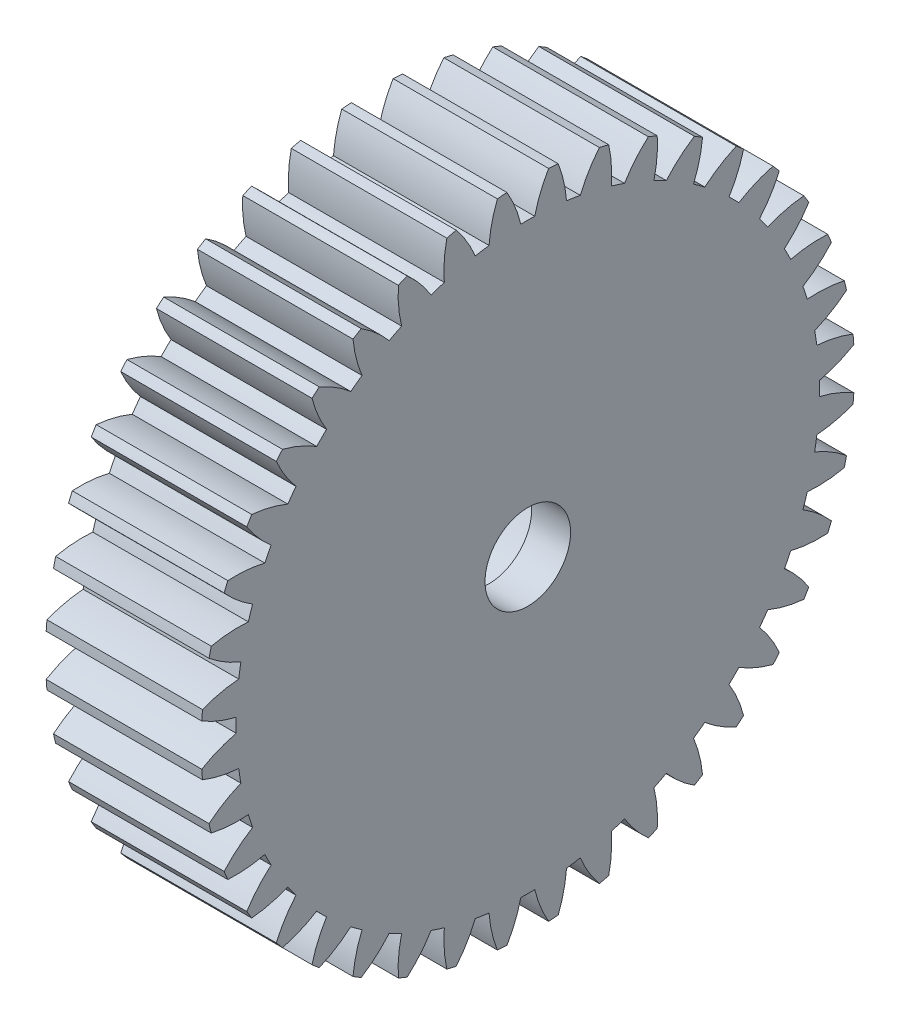
SolidWorks part; units mm, degrees
ref_plane "Front Plane" through (0, 0, 0) normal (0, 0, 1) x (1, 0, 0)
ref_plane "Top Plane" through (0, 0, 0) normal (0, 1, 0) x (1, 0, 0)
ref_plane "Right Plane" through (0, 0, 0) normal (1, 0, 0) x (0, 0, -1)
ref_plane "Plane1" through (-1.595, 0, 0) normal (1, 0, 0) x (0, 0, -1)
sketch "Sketch1" plane through (-1.595, 0, 0) normal (1, 0, 0) x (0, 0, -1)
  circle B0 centre (0, 0) radius 0.4
  arc B1 (-8.3829, 0.5357) -> (-7.4969, 0.179) centre (-6.7581, 3.2926) ccw
  arc B2 (-7.4969, 0.179) -> (-7.4969, -0.179) centre (0, 0) ccw
  arc B3 (-7.4969, -0.179) -> (-8.3829, -0.5357) centre (-6.7581, -3.2926) ccw
  arc B4 (-8.3829, -0.5357) -> (-8.3635, -0.7822) centre (0, 0) ccw
  arc B5 (-8.3635, -0.7822) -> (-7.4326, -0.996) centre (-7.19, 2.1948) ccw
  arc B6 (-7.4326, -0.996) -> (-7.3766, -1.3496) centre (0, 0) ccw
  arc B7 (-7.3766, -1.3496) -> (-8.1959, -1.8405) centre (-6.1599, -4.3092) ccw
  arc B8 (-8.1959, -1.8405) -> (-8.1382, -2.081) centre (0, 0) ccw
  arc B9 (-8.1382, -2.081) -> (-7.1853, -2.1464) centre (-7.4448, 1.043) ccw
  arc B10 (-7.1853, -2.1464) -> (-7.0746, -2.4869) centre (0, 0) ccw
  arc B11 (-7.0746, -2.4869) -> (-7.8071, -3.1) centre (-5.4099, -5.2198) ccw
  arc B12 (-7.8071, -3.1) -> (-7.7124, -3.3284) centre (0, 0) ccw
  arc B13 (-7.7124, -3.3284) -> (-6.761, -3.244) centre (-7.5163, -0.1344) ccw
  arc B14 (-6.761, -3.244) -> (-6.5985, -3.563) centre (0, 0) ccw
  arc B15 (-6.5985, -3.563) -> (-7.226, -4.2831) centre (-4.5268, -6.0018) ccw
  arc B16 (-7.226, -4.2831) -> (-7.0968, -4.4939) centre (0, 0) ccw
  arc B17 (-7.0968, -4.4939) -> (-6.1703, -4.2617) centre (-7.4028, -1.3086) ccw
  arc B18 (-6.1703, -4.2617) -> (-5.9599, -4.5514) centre (0, 0) ccw
  arc B19 (-5.9599, -4.5514) -> (-6.467, -5.3608) centre (-3.5321, -6.6361) ccw
  arc B20 (-6.467, -5.3608) -> (-6.3064, -5.5488) centre (0, 0) ccw
  arc B21 (-6.3064, -5.5488) -> (-5.4277, -5.1745) centre (-7.1069, -2.4505) ccw
  arc B22 (-5.4277, -5.1745) -> (-5.1745, -5.4277) centre (0, 0) ccw
  arc B23 (-5.1745, -5.4277) -> (-5.5488, -6.3064) centre (-2.4505, -7.1069) ccw
  arc B24 (-5.5488, -6.3064) -> (-5.3608, -6.467) centre (0, 0) ccw
  arc B25 (-5.3608, -6.467) -> (-4.5514, -5.9599) centre (-6.6361, -3.5321) ccw
  arc B26 (-4.5514, -5.9599) -> (-4.2617, -6.1703) centre (0, 0) ccw
  arc B27 (-4.2617, -6.1703) -> (-4.4939, -7.0968) centre (-1.3086, -7.4028) ccw
  arc B28 (-4.4939, -7.0968) -> (-4.2831, -7.226) centre (0, 0) ccw
  arc B29 (-4.2831, -7.226) -> (-3.563, -6.5985) centre (-6.0018, -4.5268) ccw
  arc B30 (-3.563, -6.5985) -> (-3.244, -6.761) centre (0, 0) ccw
  arc B31 (-3.244, -6.761) -> (-3.3284, -7.7124) centre (-0.1344, -7.5163) ccw
  arc B32 (-3.3284, -7.7124) -> (-3.1, -7.8071) centre (0, 0) ccw
  arc B33 (-3.1, -7.8071) -> (-2.4869, -7.0746) centre (-5.2198, -5.4099) ccw
  arc B34 (-2.4869, -7.0746) -> (-2.1464, -7.1853) centre (0, 0) ccw
  arc B35 (-2.1464, -7.1853) -> (-2.081, -8.1382) centre (1.043, -7.4448) ccw
  arc B36 (-2.081, -8.1382) -> (-1.8405, -8.1959) centre (0, 0) ccw
  arc B37 (-1.8405, -8.1959) -> (-1.3496, -7.3766) centre (-4.3092, -6.1599) ccw
  arc B38 (-1.3496, -7.3766) -> (-0.996, -7.4326) centre (0, 0) ccw
  arc B39 (-0.996, -7.4326) -> (-0.7822, -8.3635) centre (2.1948, -7.19) ccw
  arc B40 (-0.7822, -8.3635) -> (-0.5357, -8.3829) centre (0, 0) ccw
  arc B41 (-0.5357, -8.3829) -> (-0.179, -7.4969) centre (-3.2926, -6.7581) ccw
  arc B42 (-0.179, -7.4969) -> (0.179, -7.4969) centre (0, 0) ccw
  arc B43 (0.179, -7.4969) -> (0.5357, -8.3829) centre (3.2926, -6.7581) ccw
  arc B44 (0.5357, -8.3829) -> (0.7822, -8.3635) centre (0, 0) ccw
  arc B45 (0.7822, -8.3635) -> (0.996, -7.4326) centre (-2.1948, -7.19) ccw
  arc B46 (0.996, -7.4326) -> (1.3496, -7.3766) centre (0, 0) ccw
  arc B47 (1.3496, -7.3766) -> (1.8405, -8.1959) centre (4.3092, -6.1599) ccw
  arc B48 (1.8405, -8.1959) -> (2.081, -8.1382) centre (0, 0) ccw
  arc B49 (2.081, -8.1382) -> (2.1464, -7.1853) centre (-1.043, -7.4448) ccw
  arc B50 (2.1464, -7.1853) -> (2.4869, -7.0746) centre (0, 0) ccw
  arc B51 (2.4869, -7.0746) -> (3.1, -7.8071) centre (5.2198, -5.4099) ccw
  arc B52 (3.1, -7.8071) -> (3.3284, -7.7124) centre (0, 0) ccw
  arc B53 (3.3284, -7.7124) -> (3.244, -6.761) centre (0.1344, -7.5163) ccw
  arc B54 (3.244, -6.761) -> (3.563, -6.5985) centre (0, 0) ccw
  arc B55 (3.563, -6.5985) -> (4.2831, -7.226) centre (6.0018, -4.5268) ccw
  arc B56 (4.2831, -7.226) -> (4.4939, -7.0968) centre (0, 0) ccw
  arc B57 (4.4939, -7.0968) -> (4.2617, -6.1703) centre (1.3086, -7.4028) ccw
  arc B58 (4.2617, -6.1703) -> (4.5514, -5.9599) centre (0, 0) ccw
  arc B59 (4.5514, -5.9599) -> (5.3608, -6.467) centre (6.6361, -3.5321) ccw
  arc B60 (5.3608, -6.467) -> (5.5488, -6.3064) centre (0, 0) ccw
  arc B61 (5.5488, -6.3064) -> (5.1745, -5.4277) centre (2.4505, -7.1069) ccw
  arc B62 (5.1745, -5.4277) -> (5.4277, -5.1745) centre (0, 0) ccw
  arc B63 (5.4277, -5.1745) -> (6.3064, -5.5488) centre (7.1069, -2.4505) ccw
  arc B64 (6.3064, -5.5488) -> (6.467, -5.3608) centre (0, 0) ccw
  arc B65 (6.467, -5.3608) -> (5.9599, -4.5514) centre (3.5321, -6.6361) ccw
  arc B66 (5.9599, -4.5514) -> (6.1703, -4.2617) centre (0, 0) ccw
  arc B67 (6.1703, -4.2617) -> (7.0968, -4.4939) centre (7.4028, -1.3086) ccw
  arc B68 (7.0968, -4.4939) -> (7.226, -4.2831) centre (0, 0) ccw
  arc B69 (7.226, -4.2831) -> (6.5985, -3.563) centre (4.5268, -6.0018) ccw
  arc B70 (6.5985, -3.563) -> (6.761, -3.244) centre (0, 0) ccw
  arc B71 (6.761, -3.244) -> (7.7124, -3.3284) centre (7.5163, -0.1344) ccw
  arc B72 (7.7124, -3.3284) -> (7.8071, -3.1) centre (0, 0) ccw
  arc B73 (7.8071, -3.1) -> (7.0746, -2.4869) centre (5.4099, -5.2198) ccw
  arc B74 (7.0746, -2.4869) -> (7.1853, -2.1464) centre (0, 0) ccw
  arc B75 (7.1853, -2.1464) -> (8.1382, -2.081) centre (7.4448, 1.043) ccw
  arc B76 (8.1382, -2.081) -> (8.1959, -1.8405) centre (0, 0) ccw
  arc B77 (8.1959, -1.8405) -> (7.3766, -1.3496) centre (6.1599, -4.3092) ccw
  arc B78 (7.3766, -1.3496) -> (7.4326, -0.996) centre (0, 0) ccw
  arc B79 (7.4326, -0.996) -> (8.3635, -0.7822) centre (7.19, 2.1948) ccw
  arc B80 (8.3635, -0.7822) -> (8.3829, -0.5357) centre (0, 0) ccw
  arc B81 (8.3829, -0.5357) -> (7.4969, -0.179) centre (6.7581, -3.2926) ccw
  arc B82 (7.4969, -0.179) -> (7.4969, 0.179) centre (0, 0) ccw
  arc B83 (7.4969, 0.179) -> (8.3829, 0.5357) centre (6.7581, 3.2926) ccw
  arc B84 (8.3829, 0.5357) -> (8.3635, 0.7822) centre (0, 0) ccw
  arc B85 (8.3635, 0.7822) -> (7.4326, 0.996) centre (7.19, -2.1948) ccw
  arc B86 (7.4326, 0.996) -> (7.3766, 1.3496) centre (0, 0) ccw
  arc B87 (7.3766, 1.3496) -> (8.1959, 1.8405) centre (6.1599, 4.3092) ccw
  arc B88 (8.1959, 1.8405) -> (8.1382, 2.081) centre (0, 0) ccw
  arc B89 (8.1382, 2.081) -> (7.1853, 2.1464) centre (7.4448, -1.043) ccw
  arc B90 (7.1853, 2.1464) -> (7.0746, 2.4869) centre (0, 0) ccw
  arc B91 (7.0746, 2.4869) -> (7.8071, 3.1) centre (5.4099, 5.2198) ccw
  arc B92 (7.8071, 3.1) -> (7.7124, 3.3284) centre (0, 0) ccw
  arc B93 (7.7124, 3.3284) -> (6.761, 3.244) centre (7.5163, 0.1344) ccw
  arc B94 (6.761, 3.244) -> (6.5985, 3.563) centre (0, 0) ccw
  arc B95 (6.5985, 3.563) -> (7.226, 4.2831) centre (4.5268, 6.0018) ccw
  arc B96 (7.226, 4.2831) -> (7.0968, 4.4939) centre (0, 0) ccw
  arc B97 (7.0968, 4.4939) -> (6.1703, 4.2617) centre (7.4028, 1.3086) ccw
  arc B98 (6.1703, 4.2617) -> (5.9599, 4.5514) centre (0, 0) ccw
  arc B99 (5.9599, 4.5514) -> (6.467, 5.3608) centre (3.5321, 6.6361) ccw
  arc B100 (6.467, 5.3608) -> (6.3064, 5.5488) centre (0, 0) ccw
  arc B101 (6.3064, 5.5488) -> (5.4277, 5.1745) centre (7.1069, 2.4505) ccw
  arc B102 (5.4277, 5.1745) -> (5.1745, 5.4277) centre (0, 0) ccw
  arc B103 (5.1745, 5.4277) -> (5.5488, 6.3064) centre (2.4505, 7.1069) ccw
  arc B104 (5.5488, 6.3064) -> (5.3608, 6.467) centre (0, 0) ccw
  arc B105 (5.3608, 6.467) -> (4.5514, 5.9599) centre (6.6361, 3.5321) ccw
  arc B106 (4.5514, 5.9599) -> (4.2617, 6.1703) centre (0, 0) ccw
  arc B107 (4.2617, 6.1703) -> (4.4939, 7.0968) centre (1.3086, 7.4028) ccw
  arc B108 (4.4939, 7.0968) -> (4.2831, 7.226) centre (0, 0) ccw
  arc B109 (4.2831, 7.226) -> (3.563, 6.5985) centre (6.0018, 4.5268) ccw
  arc B110 (3.563, 6.5985) -> (3.244, 6.761) centre (0, 0) ccw
  arc B111 (3.244, 6.761) -> (3.3284, 7.7124) centre (0.1344, 7.5163) ccw
  arc B112 (3.3284, 7.7124) -> (3.1, 7.8071) centre (0, 0) ccw
  arc B113 (3.1, 7.8071) -> (2.4869, 7.0746) centre (5.2198, 5.4099) ccw
  arc B114 (2.4869, 7.0746) -> (2.1464, 7.1853) centre (0, 0) ccw
  arc B115 (2.1464, 7.1853) -> (2.081, 8.1382) centre (-1.043, 7.4448) ccw
  arc B116 (2.081, 8.1382) -> (1.8405, 8.1959) centre (0, 0) ccw
  arc B117 (1.8405, 8.1959) -> (1.3496, 7.3766) centre (4.3092, 6.1599) ccw
  arc B118 (1.3496, 7.3766) -> (0.996, 7.4326) centre (0, 0) ccw
  arc B119 (0.996, 7.4326) -> (0.7822, 8.3635) centre (-2.1948, 7.19) ccw
  arc B120 (0.7822, 8.3635) -> (0.5357, 8.3829) centre (0, 0) ccw
  arc B121 (0.5357, 8.3829) -> (0.179, 7.4969) centre (3.2926, 6.7581) ccw
  arc B122 (0.179, 7.4969) -> (-0.179, 7.4969) centre (0, 0) ccw
  arc B123 (-0.179, 7.4969) -> (-0.5357, 8.3829) centre (-3.2926, 6.7581) ccw
  arc B124 (-0.5357, 8.3829) -> (-0.7822, 8.3635) centre (0, 0) ccw
  arc B125 (-0.7822, 8.3635) -> (-0.996, 7.4326) centre (2.1948, 7.19) ccw
  arc B126 (-0.996, 7.4326) -> (-1.3496, 7.3766) centre (0, 0) ccw
  arc B127 (-1.3496, 7.3766) -> (-1.8405, 8.1959) centre (-4.3092, 6.1599) ccw
  arc B128 (-1.8405, 8.1959) -> (-2.081, 8.1382) centre (0, 0) ccw
  arc B129 (-2.081, 8.1382) -> (-2.1464, 7.1853) centre (1.043, 7.4448) ccw
  arc B130 (-2.1464, 7.1853) -> (-2.4869, 7.0746) centre (0, 0) ccw
  arc B131 (-2.4869, 7.0746) -> (-3.1, 7.8071) centre (-5.2198, 5.4099) ccw
  arc B132 (-3.1, 7.8071) -> (-3.3284, 7.7124) centre (0, 0) ccw
  arc B133 (-3.3284, 7.7124) -> (-3.244, 6.761) centre (-0.1344, 7.5163) ccw
  arc B134 (-3.244, 6.761) -> (-3.563, 6.5985) centre (0, 0) ccw
  arc B135 (-3.563, 6.5985) -> (-4.2831, 7.226) centre (-6.0018, 4.5268) ccw
  arc B136 (-4.2831, 7.226) -> (-4.4939, 7.0968) centre (0, 0) ccw
  arc B137 (-4.4939, 7.0968) -> (-4.2617, 6.1703) centre (-1.3086, 7.4028) ccw
  arc B138 (-4.2617, 6.1703) -> (-4.5514, 5.9599) centre (0, 0) ccw
  arc B139 (-4.5514, 5.9599) -> (-5.3608, 6.467) centre (-6.6361, 3.5321) ccw
  arc B140 (-5.3608, 6.467) -> (-5.5488, 6.3064) centre (0, 0) ccw
  arc B141 (-5.5488, 6.3064) -> (-5.1745, 5.4277) centre (-2.4505, 7.1069) ccw
  arc B142 (-5.1745, 5.4277) -> (-5.4277, 5.1745) centre (0, 0) ccw
  arc B143 (-5.4277, 5.1745) -> (-6.3064, 5.5488) centre (-7.1069, 2.4505) ccw
  arc B144 (-6.3064, 5.5488) -> (-6.467, 5.3608) centre (0, 0) ccw
  arc B145 (-6.467, 5.3608) -> (-5.9599, 4.5514) centre (-3.5321, 6.6361) ccw
  arc B146 (-5.9599, 4.5514) -> (-6.1703, 4.2617) centre (0, 0) ccw
  arc B147 (-6.1703, 4.2617) -> (-7.0968, 4.4939) centre (-7.4028, 1.3086) ccw
  arc B148 (-7.0968, 4.4939) -> (-7.226, 4.2831) centre (0, 0) ccw
  arc B149 (-7.226, 4.2831) -> (-6.5985, 3.563) centre (-4.5268, 6.0018) ccw
  arc B150 (-6.5985, 3.563) -> (-6.761, 3.244) centre (0, 0) ccw
  arc B151 (-6.761, 3.244) -> (-7.7124, 3.3284) centre (-7.5163, 0.1344) ccw
  arc B152 (-7.7124, 3.3284) -> (-7.8071, 3.1) centre (0, 0) ccw
  arc B153 (-7.8071, 3.1) -> (-7.0746, 2.4869) centre (-5.4099, 5.2198) ccw
  arc B154 (-7.0746, 2.4869) -> (-7.1853, 2.1464) centre (0, 0) ccw
  arc B155 (-7.1853, 2.1464) -> (-8.1382, 2.081) centre (-7.4448, -1.043) ccw
  arc B156 (-8.1382, 2.081) -> (-8.1959, 1.8405) centre (0, 0) ccw
  arc B157 (-8.1959, 1.8405) -> (-7.3766, 1.3496) centre (-6.1599, 4.3092) ccw
  arc B158 (-7.3766, 1.3496) -> (-7.4326, 0.996) centre (0, 0) ccw
  arc B159 (-7.4326, 0.996) -> (-8.3635, 0.7822) centre (-7.19, -2.1948) ccw
  arc B160 (-8.3635, 0.7822) -> (-8.3829, 0.5357) centre (0, 0) ccw
sketch_block_instance "Block2-1"
sketch_block "Block2"
extrude "Boss-Extrude1" add sketch "Sketch1" against normal blind 3
sketch "Sketch4" plane through (-1.595, 0, 0) normal (1, 0, 0) x (0, 0, -1)
  circle A0 centre (0, 0) radius 2.4375
  dimension "D1" = 4.875
extrude "Cut-Extrude2" cut sketch "Sketch4" against normal through all
sketch "Sketch5" plane through (-1.595, 0, 0) normal (1, 0, 0) x (0, 0, -1)
  arc A160 (-8.3635, 0.7822) -> (-8.3829, 0.5357) centre (0, 0) ccw
  arc A161 (-8.3829, 0.5357) -> (-7.4969, 0.179) centre (-6.7581, 3.2926) ccw
  arc A162 (-7.4969, 0.179) -> (-7.4969, -0.179) centre (0, 0) ccw
  arc A163 (-7.4969, -0.179) -> (-8.3829, -0.5357) centre (-6.7581, -3.2926) ccw
  arc A164 (-8.3829, -0.5357) -> (-8.3635, -0.7822) centre (0, 0) ccw
  arc A165 (-8.3635, -0.7822) -> (-7.4326, -0.996) centre (-7.19, 2.1948) ccw
  arc A166 (-7.4326, -0.996) -> (-7.3766, -1.3496) centre (0, 0) ccw
  arc A167 (-7.3766, -1.3496) -> (-8.1959, -1.8405) centre (-6.1599, -4.3092) ccw
  arc A168 (-8.1959, -1.8405) -> (-8.1382, -2.081) centre (0, 0) ccw
  arc A169 (-8.1382, -2.081) -> (-7.1853, -2.1464) centre (-7.4448, 1.043) ccw
  arc A170 (-7.1853, -2.1464) -> (-7.0746, -2.4869) centre (0, 0) ccw
  arc A171 (-7.0746, -2.4869) -> (-7.8071, -3.1) centre (-5.4099, -5.2198) ccw
  arc A172 (-7.8071, -3.1) -> (-7.7124, -3.3284) centre (0, 0) ccw
  arc A173 (-7.7124, -3.3284) -> (-6.761, -3.244) centre (-7.5163, -0.1344) ccw
  arc A174 (-6.761, -3.244) -> (-6.5985, -3.563) centre (0, 0) ccw
  arc A175 (-6.5985, -3.563) -> (-7.226, -4.2831) centre (-4.5268, -6.0018) ccw
  arc A176 (-7.226, -4.2831) -> (-7.0968, -4.4939) centre (0, 0) ccw
  arc A177 (-7.0968, -4.4939) -> (-6.1703, -4.2617) centre (-7.4028, -1.3086) ccw
  arc A178 (-6.1703, -4.2617) -> (-5.9599, -4.5514) centre (0, 0) ccw
  arc A179 (-5.9599, -4.5514) -> (-6.467, -5.3608) centre (-3.5321, -6.6361) ccw
  arc A180 (-6.467, -5.3608) -> (-6.3064, -5.5488) centre (0, 0) ccw
  arc A181 (-6.3064, -5.5488) -> (-5.4277, -5.1745) centre (-7.1069, -2.4505) ccw
  arc A182 (-5.4277, -5.1745) -> (-5.1745, -5.4277) centre (0, 0) ccw
  arc A183 (-5.1745, -5.4277) -> (-5.5488, -6.3064) centre (-2.4505, -7.1069) ccw
  arc A184 (-5.5488, -6.3064) -> (-5.3608, -6.467) centre (0, 0) ccw
  arc A185 (-5.3608, -6.467) -> (-4.5514, -5.9599) centre (-6.6361, -3.5321) ccw
  arc A186 (-4.5514, -5.9599) -> (-4.2617, -6.1703) centre (0, 0) ccw
  arc A187 (-4.2617, -6.1703) -> (-4.4939, -7.0968) centre (-1.3086, -7.4028) ccw
  arc A188 (-4.4939, -7.0968) -> (-4.2831, -7.226) centre (0, 0) ccw
  arc A189 (-4.2831, -7.226) -> (-3.563, -6.5985) centre (-6.0018, -4.5268) ccw
  arc A190 (-3.563, -6.5985) -> (-3.244, -6.761) centre (0, 0) ccw
  arc A191 (-3.244, -6.761) -> (-3.3284, -7.7124) centre (-0.1344, -7.5163) ccw
  arc A192 (-3.3284, -7.7124) -> (-3.1, -7.8071) centre (0, 0) ccw
  arc A193 (-3.1, -7.8071) -> (-2.4869, -7.0746) centre (-5.2198, -5.4099) ccw
  arc A194 (-2.4869, -7.0746) -> (-2.1464, -7.1853) centre (0, 0) ccw
  arc A195 (-2.1464, -7.1853) -> (-2.081, -8.1382) centre (1.043, -7.4448) ccw
  arc A196 (-2.081, -8.1382) -> (-1.8405, -8.1959) centre (0, 0) ccw
  arc A197 (-1.8405, -8.1959) -> (-1.3496, -7.3766) centre (-4.3092, -6.1599) ccw
  arc A198 (-1.3496, -7.3766) -> (-0.996, -7.4326) centre (0, 0) ccw
  arc A199 (-0.996, -7.4326) -> (-0.7822, -8.3635) centre (2.1948, -7.19) ccw
  arc A200 (-0.7822, -8.3635) -> (-0.5357, -8.3829) centre (0, 0) ccw
  arc A201 (-0.5357, -8.3829) -> (-0.179, -7.4969) centre (-3.2926, -6.7581) ccw
  arc A202 (-0.179, -7.4969) -> (0.179, -7.4969) centre (0, 0) ccw
  arc A203 (0.179, -7.4969) -> (0.5357, -8.3829) centre (3.2926, -6.7581) ccw
  arc A204 (0.5357, -8.3829) -> (0.7822, -8.3635) centre (0, 0) ccw
  arc A205 (0.7822, -8.3635) -> (0.996, -7.4326) centre (-2.1948, -7.19) ccw
  arc A206 (0.996, -7.4326) -> (1.3496, -7.3766) centre (0, 0) ccw
  arc A207 (1.3496, -7.3766) -> (1.8405, -8.1959) centre (4.3092, -6.1599) ccw
  arc A208 (1.8405, -8.1959) -> (2.081, -8.1382) centre (0, 0) ccw
  arc A209 (2.081, -8.1382) -> (2.1464, -7.1853) centre (-1.043, -7.4448) ccw
  arc A210 (2.1464, -7.1853) -> (2.4869, -7.0746) centre (0, 0) ccw
  arc A211 (2.4869, -7.0746) -> (3.1, -7.8071) centre (5.2198, -5.4099) ccw
  arc A212 (3.1, -7.8071) -> (3.3284, -7.7124) centre (0, 0) ccw
  arc A213 (3.3284, -7.7124) -> (3.244, -6.761) centre (0.1344, -7.5163) ccw
  arc A214 (3.244, -6.761) -> (3.563, -6.5985) centre (0, 0) ccw
  arc A215 (3.563, -6.5985) -> (4.2831, -7.226) centre (6.0018, -4.5268) ccw
  arc A216 (4.2831, -7.226) -> (4.4939, -7.0968) centre (0, 0) ccw
  arc A217 (4.4939, -7.0968) -> (4.2617, -6.1703) centre (1.3086, -7.4028) ccw
  arc A218 (4.2617, -6.1703) -> (4.5514, -5.9599) centre (0, 0) ccw
  arc A219 (4.5514, -5.9599) -> (5.3608, -6.467) centre (6.6361, -3.5321) ccw
  arc A220 (5.3608, -6.467) -> (5.5488, -6.3064) centre (0, 0) ccw
  arc A221 (5.5488, -6.3064) -> (5.1745, -5.4277) centre (2.4505, -7.1069) ccw
  arc A222 (5.1745, -5.4277) -> (5.4277, -5.1745) centre (0, 0) ccw
  arc A223 (5.4277, -5.1745) -> (6.3064, -5.5488) centre (7.1069, -2.4505) ccw
  arc A224 (6.3064, -5.5488) -> (6.467, -5.3608) centre (0, 0) ccw
  arc A225 (6.467, -5.3608) -> (5.9599, -4.5514) centre (3.5321, -6.6361) ccw
  arc A226 (5.9599, -4.5514) -> (6.1703, -4.2617) centre (0, 0) ccw
  arc A227 (6.1703, -4.2617) -> (7.0968, -4.4939) centre (7.4028, -1.3086) ccw
  arc A228 (7.0968, -4.4939) -> (7.226, -4.2831) centre (0, 0) ccw
  arc A229 (7.226, -4.2831) -> (6.5985, -3.563) centre (4.5268, -6.0018) ccw
  arc A230 (6.5985, -3.563) -> (6.761, -3.244) centre (0, 0) ccw
  arc A231 (6.761, -3.244) -> (7.7124, -3.3284) centre (7.5163, -0.1344) ccw
  arc A232 (7.7124, -3.3284) -> (7.8071, -3.1) centre (0, 0) ccw
  arc A233 (7.8071, -3.1) -> (7.0746, -2.4869) centre (5.4099, -5.2198) ccw
  arc A234 (7.0746, -2.4869) -> (7.1853, -2.1464) centre (0, 0) ccw
  arc A235 (7.1853, -2.1464) -> (8.1382, -2.081) centre (7.4448, 1.043) ccw
  arc A236 (8.1382, -2.081) -> (8.1959, -1.8405) centre (0, 0) ccw
  arc A237 (8.1959, -1.8405) -> (7.3766, -1.3496) centre (6.1599, -4.3092) ccw
  arc A238 (7.3766, -1.3496) -> (7.4326, -0.996) centre (0, 0) ccw
  arc A239 (7.4326, -0.996) -> (8.3635, -0.7822) centre (7.19, 2.1948) ccw
  arc A240 (8.3635, -0.7822) -> (8.3829, -0.5357) centre (0, 0) ccw
  arc A241 (8.3829, -0.5357) -> (7.4969, -0.179) centre (6.7581, -3.2926) ccw
  arc A242 (7.4969, -0.179) -> (7.4969, 0.179) centre (0, 0) ccw
  arc A243 (7.4969, 0.179) -> (8.3829, 0.5357) centre (6.7581, 3.2926) ccw
  arc A244 (8.3829, 0.5357) -> (8.3635, 0.7822) centre (0, 0) ccw
  arc A245 (8.3635, 0.7822) -> (7.4326, 0.996) centre (7.19, -2.1948) ccw
  arc A246 (7.4326, 0.996) -> (7.3766, 1.3496) centre (0, 0) ccw
  arc A247 (7.3766, 1.3496) -> (8.1959, 1.8405) centre (6.1599, 4.3092) ccw
  arc A248 (8.1959, 1.8405) -> (8.1382, 2.081) centre (0, 0) ccw
  arc A249 (8.1382, 2.081) -> (7.1853, 2.1464) centre (7.4448, -1.043) ccw
  arc A250 (7.1853, 2.1464) -> (7.0746, 2.4869) centre (0, 0) ccw
  arc A251 (7.0746, 2.4869) -> (7.8071, 3.1) centre (5.4099, 5.2198) ccw
  arc A252 (7.8071, 3.1) -> (7.7124, 3.3284) centre (0, 0) ccw
  arc A253 (7.7124, 3.3284) -> (6.761, 3.244) centre (7.5163, 0.1344) ccw
  arc A254 (6.761, 3.244) -> (6.5985, 3.563) centre (0, 0) ccw
  arc A255 (6.5985, 3.563) -> (7.226, 4.2831) centre (4.5268, 6.0018) ccw
  arc A256 (7.226, 4.2831) -> (7.0968, 4.4939) centre (0, 0) ccw
  arc A257 (7.0968, 4.4939) -> (6.1703, 4.2617) centre (7.4028, 1.3086) ccw
  arc A258 (6.1703, 4.2617) -> (5.9599, 4.5514) centre (0, 0) ccw
  arc A259 (5.9599, 4.5514) -> (6.467, 5.3608) centre (3.5321, 6.6361) ccw
  arc A260 (6.467, 5.3608) -> (6.3064, 5.5488) centre (0, 0) ccw
  arc A261 (6.3064, 5.5488) -> (5.4277, 5.1745) centre (7.1069, 2.4505) ccw
  arc A262 (5.4277, 5.1745) -> (5.1745, 5.4277) centre (0, 0) ccw
  arc A263 (5.1745, 5.4277) -> (5.5488, 6.3064) centre (2.4505, 7.1069) ccw
  arc A264 (5.5488, 6.3064) -> (5.3608, 6.467) centre (0, 0) ccw
  arc A265 (5.3608, 6.467) -> (4.5514, 5.9599) centre (6.6361, 3.5321) ccw
  arc A266 (4.5514, 5.9599) -> (4.2617, 6.1703) centre (0, 0) ccw
  arc A267 (4.2617, 6.1703) -> (4.4939, 7.0968) centre (1.3086, 7.4028) ccw
  arc A268 (4.4939, 7.0968) -> (4.2831, 7.226) centre (0, 0) ccw
  arc A269 (4.2831, 7.226) -> (3.563, 6.5985) centre (6.0018, 4.5268) ccw
  arc A270 (3.563, 6.5985) -> (3.244, 6.761) centre (0, 0) ccw
  arc A271 (3.244, 6.761) -> (3.3284, 7.7124) centre (0.1344, 7.5163) ccw
  arc A272 (3.3284, 7.7124) -> (3.1, 7.8071) centre (0, 0) ccw
  arc A273 (3.1, 7.8071) -> (2.4869, 7.0746) centre (5.2198, 5.4099) ccw
  arc A274 (2.4869, 7.0746) -> (2.1464, 7.1853) centre (0, 0) ccw
  arc A275 (2.1464, 7.1853) -> (2.081, 8.1382) centre (-1.043, 7.4448) ccw
  arc A276 (2.081, 8.1382) -> (1.8405, 8.1959) centre (0, 0) ccw
  arc A277 (1.8405, 8.1959) -> (1.3496, 7.3766) centre (4.3092, 6.1599) ccw
  arc A278 (1.3496, 7.3766) -> (0.996, 7.4326) centre (0, 0) ccw
  arc A279 (0.996, 7.4326) -> (0.7822, 8.3635) centre (-2.1948, 7.19) ccw
  arc A280 (0.7822, 8.3635) -> (0.5357, 8.3829) centre (0, 0) ccw
  arc A281 (0.5357, 8.3829) -> (0.179, 7.4969) centre (3.2926, 6.7581) ccw
  arc A282 (0.179, 7.4969) -> (-0.179, 7.4969) centre (0, 0) ccw
  arc A283 (-0.179, 7.4969) -> (-0.5357, 8.3829) centre (-3.2926, 6.7581) ccw
  arc A284 (-0.5357, 8.3829) -> (-0.7822, 8.3635) centre (0, 0) ccw
  arc A285 (-0.7822, 8.3635) -> (-0.996, 7.4326) centre (2.1948, 7.19) ccw
  arc A286 (-0.996, 7.4326) -> (-1.3496, 7.3766) centre (0, 0) ccw
  arc A287 (-1.3496, 7.3766) -> (-1.8405, 8.1959) centre (-4.3092, 6.1599) ccw
  arc A288 (-1.8405, 8.1959) -> (-2.081, 8.1382) centre (0, 0) ccw
  arc A289 (-2.081, 8.1382) -> (-2.1464, 7.1853) centre (1.043, 7.4448) ccw
  arc A290 (-2.1464, 7.1853) -> (-2.4869, 7.0746) centre (0, 0) ccw
  arc A291 (-2.4869, 7.0746) -> (-3.1, 7.8071) centre (-5.2198, 5.4099) ccw
  arc A292 (-3.1, 7.8071) -> (-3.3284, 7.7124) centre (0, 0) ccw
  arc A293 (-3.3284, 7.7124) -> (-3.244, 6.761) centre (-0.1344, 7.5163) ccw
  arc A294 (-3.244, 6.761) -> (-3.563, 6.5985) centre (0, 0) ccw
  arc A295 (-3.563, 6.5985) -> (-4.2831, 7.226) centre (-6.0018, 4.5268) ccw
  arc A296 (-4.2831, 7.226) -> (-4.4939, 7.0968) centre (0, 0) ccw
  arc A297 (-4.4939, 7.0968) -> (-4.2617, 6.1703) centre (-1.3086, 7.4028) ccw
  arc A298 (-4.2617, 6.1703) -> (-4.5514, 5.9599) centre (0, 0) ccw
  arc A299 (-4.5514, 5.9599) -> (-5.3608, 6.467) centre (-6.6361, 3.5321) ccw
  arc A300 (-5.3608, 6.467) -> (-5.5488, 6.3064) centre (0, 0) ccw
  arc A301 (-5.5488, 6.3064) -> (-5.1745, 5.4277) centre (-2.4505, 7.1069) ccw
  arc A302 (-5.1745, 5.4277) -> (-5.4277, 5.1745) centre (0, 0) ccw
  arc A303 (-5.4277, 5.1745) -> (-6.3064, 5.5488) centre (-7.1069, 2.4505) ccw
  arc A304 (-6.3064, 5.5488) -> (-6.467, 5.3608) centre (0, 0) ccw
  arc A305 (-6.467, 5.3608) -> (-5.9599, 4.5514) centre (-3.5321, 6.6361) ccw
  arc A306 (-5.9599, 4.5514) -> (-6.1703, 4.2617) centre (0, 0) ccw
  arc A307 (-6.1703, 4.2617) -> (-7.0968, 4.4939) centre (-7.4028, 1.3086) ccw
  arc A308 (-7.0968, 4.4939) -> (-7.226, 4.2831) centre (0, 0) ccw
  arc A309 (-7.226, 4.2831) -> (-6.5985, 3.563) centre (-4.5268, 6.0018) ccw
  arc A310 (-6.5985, 3.563) -> (-6.761, 3.244) centre (0, 0) ccw
  arc A311 (-6.761, 3.244) -> (-7.7124, 3.3284) centre (-7.5163, 0.1344) ccw
  arc A312 (-7.7124, 3.3284) -> (-7.8071, 3.1) centre (0, 0) ccw
  arc A313 (-7.8071, 3.1) -> (-7.0746, 2.4869) centre (-5.4099, 5.2198) ccw
  arc A314 (-7.0746, 2.4869) -> (-7.1853, 2.1464) centre (0, 0) ccw
  arc A315 (-7.1853, 2.1464) -> (-8.1382, 2.081) centre (-7.4448, -1.043) ccw
  arc A316 (-8.1382, 2.081) -> (-8.1959, 1.8405) centre (0, 0) ccw
  arc A317 (-8.1959, 1.8405) -> (-7.3766, 1.3496) centre (-6.1599, 4.3092) ccw
  arc A318 (-7.3766, 1.3496) -> (-7.4326, 0.996) centre (0, 0) ccw
  arc A319 (-7.4326, 0.996) -> (-8.3635, 0.7822) centre (-7.19, -2.1948) ccw
  arc A320 (-8.3635, 0.7822) -> (-8.3829, 0.5357) centre (0, 0) ccw
  arc A321 (-8.3829, 0.5357) -> (-7.4969, 0.179) centre (-6.7581, 3.2926) ccw
  arc A322 (-7.4969, 0.179) -> (-7.4969, -0.179) centre (0, 0) ccw
  arc A323 (-7.4969, -0.179) -> (-8.3829, -0.5357) centre (-6.7581, -3.2926) ccw
  arc A324 (-8.3829, -0.5357) -> (-8.3635, -0.7822) centre (0, 0) ccw
  arc A325 (-8.3635, -0.7822) -> (-7.4326, -0.996) centre (-7.19, 2.1948) ccw
  arc A326 (-7.4326, -0.996) -> (-7.3766, -1.3496) centre (0, 0) ccw
  arc A327 (-7.3766, -1.3496) -> (-8.1959, -1.8405) centre (-6.1599, -4.3092) ccw
  arc A328 (-8.1959, -1.8405) -> (-8.1382, -2.081) centre (0, 0) ccw
  arc A329 (-8.1382, -2.081) -> (-7.1853, -2.1464) centre (-7.4448, 1.043) ccw
  arc A330 (-7.1853, -2.1464) -> (-7.0746, -2.4869) centre (0, 0) ccw
  arc A331 (-7.0746, -2.4869) -> (-7.8071, -3.1) centre (-5.4099, -5.2198) ccw
  arc A332 (-7.8071, -3.1) -> (-7.7124, -3.3284) centre (0, 0) ccw
  arc A333 (-7.7124, -3.3284) -> (-6.761, -3.244) centre (-7.5163, -0.1344) ccw
  arc A334 (-6.761, -3.244) -> (-6.5985, -3.563) centre (0, 0) ccw
  arc A335 (-6.5985, -3.563) -> (-7.226, -4.2831) centre (-4.5268, -6.0018) ccw
  arc A336 (-7.226, -4.2831) -> (-7.0968, -4.4939) centre (0, 0) ccw
  arc A337 (-7.0968, -4.4939) -> (-6.1703, -4.2617) centre (-7.4028, -1.3086) ccw
  arc A338 (-6.1703, -4.2617) -> (-5.9599, -4.5514) centre (0, 0) ccw
  arc A339 (-5.9599, -4.5514) -> (-6.467, -5.3608) centre (-3.5321, -6.6361) ccw
  arc A340 (-6.467, -5.3608) -> (-6.3064, -5.5488) centre (0, 0) ccw
  arc A341 (-6.3064, -5.5488) -> (-5.4277, -5.1745) centre (-7.1069, -2.4505) ccw
  arc A342 (-5.4277, -5.1745) -> (-5.1745, -5.4277) centre (0, 0) ccw
  arc A343 (-5.1745, -5.4277) -> (-5.5488, -6.3064) centre (-2.4505, -7.1069) ccw
  arc A344 (-5.5488, -6.3064) -> (-5.3608, -6.467) centre (0, 0) ccw
  arc A345 (-5.3608, -6.467) -> (-4.5514, -5.9599) centre (-6.6361, -3.5321) ccw
  arc A346 (-4.5514, -5.9599) -> (-4.2617, -6.1703) centre (0, 0) ccw
  arc A347 (-4.2617, -6.1703) -> (-4.4939, -7.0968) centre (-1.3086, -7.4028) ccw
  arc A348 (-4.4939, -7.0968) -> (-4.2831, -7.226) centre (0, 0) ccw
  arc A349 (-4.2831, -7.226) -> (-3.563, -6.5985) centre (-6.0018, -4.5268) ccw
  arc A350 (-3.563, -6.5985) -> (-3.244, -6.761) centre (0, 0) ccw
  arc A351 (-3.244, -6.761) -> (-3.3284, -7.7124) centre (-0.1344, -7.5163) ccw
  arc A352 (-3.3284, -7.7124) -> (-3.1, -7.8071) centre (0, 0) ccw
  arc A353 (-3.1, -7.8071) -> (-2.4869, -7.0746) centre (-5.2198, -5.4099) ccw
  arc A354 (-2.4869, -7.0746) -> (-2.1464, -7.1853) centre (0, 0) ccw
  arc A355 (-2.1464, -7.1853) -> (-2.081, -8.1382) centre (1.043, -7.4448) ccw
  arc A356 (-2.081, -8.1382) -> (-1.8405, -8.1959) centre (0, 0) ccw
  arc A357 (-1.8405, -8.1959) -> (-1.3496, -7.3766) centre (-4.3092, -6.1599) ccw
  arc A358 (-1.3496, -7.3766) -> (-0.996, -7.4326) centre (0, 0) ccw
  arc A359 (-0.996, -7.4326) -> (-0.7822, -8.3635) centre (2.1948, -7.19) ccw
  arc A360 (-0.7822, -8.3635) -> (-0.5357, -8.3829) centre (0, 0) ccw
  arc A361 (-0.5357, -8.3829) -> (-0.179, -7.4969) centre (-3.2926, -6.7581) ccw
  arc A362 (-0.179, -7.4969) -> (0.179, -7.4969) centre (0, 0) ccw
  arc A363 (0.179, -7.4969) -> (0.5357, -8.3829) centre (3.2926, -6.7581) ccw
  arc A364 (0.5357, -8.3829) -> (0.7822, -8.3635) centre (0, 0) ccw
  arc A365 (0.7822, -8.3635) -> (0.996, -7.4326) centre (-2.1948, -7.19) ccw
  arc A366 (0.996, -7.4326) -> (1.3496, -7.3766) centre (0, 0) ccw
  arc A367 (1.3496, -7.3766) -> (1.8405, -8.1959) centre (4.3092, -6.1599) ccw
  arc A368 (1.8405, -8.1959) -> (2.081, -8.1382) centre (0, 0) ccw
  arc A369 (2.081, -8.1382) -> (2.1464, -7.1853) centre (-1.043, -7.4448) ccw
  arc A370 (2.1464, -7.1853) -> (2.4869, -7.0746) centre (0, 0) ccw
  arc A371 (2.4869, -7.0746) -> (3.1, -7.8071) centre (5.2198, -5.4099) ccw
  arc A372 (3.1, -7.8071) -> (3.3284, -7.7124) centre (0, 0) ccw
  arc A373 (3.3284, -7.7124) -> (3.244, -6.761) centre (0.1344, -7.5163) ccw
  arc A374 (3.244, -6.761) -> (3.563, -6.5985) centre (0, 0) ccw
  arc A375 (3.563, -6.5985) -> (4.2831, -7.226) centre (6.0018, -4.5268) ccw
  arc A376 (4.2831, -7.226) -> (4.4939, -7.0968) centre (0, 0) ccw
  arc A377 (4.4939, -7.0968) -> (4.2617, -6.1703) centre (1.3086, -7.4028) ccw
  arc A378 (4.2617, -6.1703) -> (4.5514, -5.9599) centre (0, 0) ccw
  arc A379 (4.5514, -5.9599) -> (5.3608, -6.467) centre (6.6361, -3.5321) ccw
  arc A380 (5.3608, -6.467) -> (5.5488, -6.3064) centre (0, 0) ccw
  arc A381 (5.5488, -6.3064) -> (5.1745, -5.4277) centre (2.4505, -7.1069) ccw
  arc A382 (5.1745, -5.4277) -> (5.4277, -5.1745) centre (0, 0) ccw
  arc A383 (5.4277, -5.1745) -> (6.3064, -5.5488) centre (7.1069, -2.4505) ccw
  arc A384 (6.3064, -5.5488) -> (6.467, -5.3608) centre (0, 0) ccw
  arc A385 (6.467, -5.3608) -> (5.9599, -4.5514) centre (3.5321, -6.6361) ccw
  arc A386 (5.9599, -4.5514) -> (6.1703, -4.2617) centre (0, 0) ccw
  arc A387 (6.1703, -4.2617) -> (7.0968, -4.4939) centre (7.4028, -1.3086) ccw
  arc A388 (7.0968, -4.4939) -> (7.226, -4.2831) centre (0, 0) ccw
  arc A389 (7.226, -4.2831) -> (6.5985, -3.563) centre (4.5268, -6.0018) ccw
  arc A390 (6.5985, -3.563) -> (6.761, -3.244) centre (0, 0) ccw
  arc A391 (6.761, -3.244) -> (7.7124, -3.3284) centre (7.5163, -0.1344) ccw
  arc A392 (7.7124, -3.3284) -> (7.8071, -3.1) centre (0, 0) ccw
  arc A393 (7.8071, -3.1) -> (7.0746, -2.4869) centre (5.4099, -5.2198) ccw
  arc A394 (7.0746, -2.4869) -> (7.1853, -2.1464) centre (0, 0) ccw
  arc A395 (7.1853, -2.1464) -> (8.1382, -2.081) centre (7.4448, 1.043) ccw
  arc A396 (8.1382, -2.081) -> (8.1959, -1.8405) centre (0, 0) ccw
  arc A397 (8.1959, -1.8405) -> (7.3766, -1.3496) centre (6.1599, -4.3092) ccw
  arc A398 (7.3766, -1.3496) -> (7.4326, -0.996) centre (0, 0) ccw
  arc A399 (7.4326, -0.996) -> (8.3635, -0.7822) centre (7.19, 2.1948) ccw
  arc A400 (8.3635, -0.7822) -> (8.3829, -0.5357) centre (0, 0) ccw
  arc A401 (8.3829, -0.5357) -> (7.4969, -0.179) centre (6.7581, -3.2926) ccw
  arc A402 (7.4969, -0.179) -> (7.4969, 0.179) centre (0, 0) ccw
  arc A403 (7.4969, 0.179) -> (8.3829, 0.5357) centre (6.7581, 3.2926) ccw
  arc A404 (8.3829, 0.5357) -> (8.3635, 0.7822) centre (0, 0) ccw
  arc A405 (8.3635, 0.7822) -> (7.4326, 0.996) centre (7.19, -2.1948) ccw
  arc A406 (7.4326, 0.996) -> (7.3766, 1.3496) centre (0, 0) ccw
  arc A407 (7.3766, 1.3496) -> (8.1959, 1.8405) centre (6.1599, 4.3092) ccw
  arc A408 (8.1959, 1.8405) -> (8.1382, 2.081) centre (0, 0) ccw
  arc A409 (8.1382, 2.081) -> (7.1853, 2.1464) centre (7.4448, -1.043) ccw
  arc A410 (7.1853, 2.1464) -> (7.0746, 2.4869) centre (0, 0) ccw
  arc A411 (7.0746, 2.4869) -> (7.8071, 3.1) centre (5.4099, 5.2198) ccw
  arc A412 (7.8071, 3.1) -> (7.7124, 3.3284) centre (0, 0) ccw
  arc A413 (7.7124, 3.3284) -> (6.761, 3.244) centre (7.5163, 0.1344) ccw
  arc A414 (6.761, 3.244) -> (6.5985, 3.563) centre (0, 0) ccw
  arc A415 (6.5985, 3.563) -> (7.226, 4.2831) centre (4.5268, 6.0018) ccw
  arc A416 (7.226, 4.2831) -> (7.0968, 4.4939) centre (0, 0) ccw
  arc A417 (7.0968, 4.4939) -> (6.1703, 4.2617) centre (7.4028, 1.3086) ccw
  arc A418 (6.1703, 4.2617) -> (5.9599, 4.5514) centre (0, 0) ccw
  arc A419 (5.9599, 4.5514) -> (6.467, 5.3608) centre (3.5321, 6.6361) ccw
  arc A420 (6.467, 5.3608) -> (6.3064, 5.5488) centre (0, 0) ccw
  arc A421 (6.3064, 5.5488) -> (5.4277, 5.1745) centre (7.1069, 2.4505) ccw
  arc A422 (5.4277, 5.1745) -> (5.1745, 5.4277) centre (0, 0) ccw
  arc A423 (5.1745, 5.4277) -> (5.5488, 6.3064) centre (2.4505, 7.1069) ccw
  arc A424 (5.5488, 6.3064) -> (5.3608, 6.467) centre (0, 0) ccw
  arc A425 (5.3608, 6.467) -> (4.5514, 5.9599) centre (6.6361, 3.5321) ccw
  arc A426 (4.5514, 5.9599) -> (4.2617, 6.1703) centre (0, 0) ccw
  arc A427 (4.2617, 6.1703) -> (4.4939, 7.0968) centre (1.3086, 7.4028) ccw
  arc A428 (4.4939, 7.0968) -> (4.2831, 7.226) centre (0, 0) ccw
  arc A429 (4.2831, 7.226) -> (3.563, 6.5985) centre (6.0018, 4.5268) ccw
  arc A430 (3.563, 6.5985) -> (3.244, 6.761) centre (0, 0) ccw
  arc A431 (3.244, 6.761) -> (3.3284, 7.7124) centre (0.1344, 7.5163) ccw
  arc A432 (3.3284, 7.7124) -> (3.1, 7.8071) centre (0, 0) ccw
  arc A433 (3.1, 7.8071) -> (2.4869, 7.0746) centre (5.2198, 5.4099) ccw
  arc A434 (2.4869, 7.0746) -> (2.1464, 7.1853) centre (0, 0) ccw
  arc A435 (2.1464, 7.1853) -> (2.081, 8.1382) centre (-1.043, 7.4448) ccw
  arc A436 (2.081, 8.1382) -> (1.8405, 8.1959) centre (0, 0) ccw
  arc A437 (1.8405, 8.1959) -> (1.3496, 7.3766) centre (4.3092, 6.1599) ccw
  arc A438 (1.3496, 7.3766) -> (0.996, 7.4326) centre (0, 0) ccw
  arc A439 (0.996, 7.4326) -> (0.7822, 8.3635) centre (-2.1948, 7.19) ccw
  arc A440 (0.7822, 8.3635) -> (0.5357, 8.3829) centre (0, 0) ccw
  arc A441 (0.5357, 8.3829) -> (0.179, 7.4969) centre (3.2926, 6.7581) ccw
  arc A442 (0.179, 7.4969) -> (-0.179, 7.4969) centre (0, 0) ccw
  arc A443 (-0.179, 7.4969) -> (-0.5357, 8.3829) centre (-3.2926, 6.7581) ccw
  arc A444 (-0.5357, 8.3829) -> (-0.7822, 8.3635) centre (0, 0) ccw
  arc A445 (-0.7822, 8.3635) -> (-0.996, 7.4326) centre (2.1948, 7.19) ccw
  arc A446 (-0.996, 7.4326) -> (-1.3496, 7.3766) centre (0, 0) ccw
  arc A447 (-1.3496, 7.3766) -> (-1.8405, 8.1959) centre (-4.3092, 6.1599) ccw
  arc A448 (-1.8405, 8.1959) -> (-2.081, 8.1382) centre (0, 0) ccw
  arc A449 (-2.081, 8.1382) -> (-2.1464, 7.1853) centre (1.043, 7.4448) ccw
  arc A450 (-2.1464, 7.1853) -> (-2.4869, 7.0746) centre (0, 0) ccw
  arc A451 (-2.4869, 7.0746) -> (-3.1, 7.8071) centre (-5.2198, 5.4099) ccw
  arc A452 (-3.1, 7.8071) -> (-3.3284, 7.7124) centre (0, 0) ccw
  arc A453 (-3.3284, 7.7124) -> (-3.244, 6.761) centre (-0.1344, 7.5163) ccw
  arc A454 (-3.244, 6.761) -> (-3.563, 6.5985) centre (0, 0) ccw
  arc A455 (-3.563, 6.5985) -> (-4.2831, 7.226) centre (-6.0018, 4.5268) ccw
  arc A456 (-4.2831, 7.226) -> (-4.4939, 7.0968) centre (0, 0) ccw
  arc A457 (-4.4939, 7.0968) -> (-4.2617, 6.1703) centre (-1.3086, 7.4028) ccw
  arc A458 (-4.2617, 6.1703) -> (-4.5514, 5.9599) centre (0, 0) ccw
  arc A459 (-4.5514, 5.9599) -> (-5.3608, 6.467) centre (-6.6361, 3.5321) ccw
  arc A460 (-5.3608, 6.467) -> (-5.5488, 6.3064) centre (0, 0) ccw
  arc A461 (-5.5488, 6.3064) -> (-5.1745, 5.4277) centre (-2.4505, 7.1069) ccw
  arc A462 (-5.1745, 5.4277) -> (-5.4277, 5.1745) centre (0, 0) ccw
  arc A463 (-5.4277, 5.1745) -> (-6.3064, 5.5488) centre (-7.1069, 2.4505) ccw
  arc A464 (-6.3064, 5.5488) -> (-6.467, 5.3608) centre (0, 0) ccw
  arc A465 (-6.467, 5.3608) -> (-5.9599, 4.5514) centre (-3.5321, 6.6361) ccw
  arc A466 (-5.9599, 4.5514) -> (-6.1703, 4.2617) centre (0, 0) ccw
  arc A467 (-6.1703, 4.2617) -> (-7.0968, 4.4939) centre (-7.4028, 1.3086) ccw
  arc A468 (-7.0968, 4.4939) -> (-7.226, 4.2831) centre (0, 0) ccw
  arc A469 (-7.226, 4.2831) -> (-6.5985, 3.563) centre (-4.5268, 6.0018) ccw
  arc A470 (-6.5985, 3.563) -> (-6.761, 3.244) centre (0, 0) ccw
  arc A471 (-6.761, 3.244) -> (-7.7124, 3.3284) centre (-7.5163, 0.1344) ccw
  arc A472 (-7.7124, 3.3284) -> (-7.8071, 3.1) centre (0, 0) ccw
  arc A473 (-7.8071, 3.1) -> (-7.0746, 2.4869) centre (-5.4099, 5.2198) ccw
  arc A474 (-7.0746, 2.4869) -> (-7.1853, 2.1464) centre (0, 0) ccw
  arc A475 (-7.1853, 2.1464) -> (-8.1382, 2.081) centre (-7.4448, -1.043) ccw
  arc A476 (-8.1382, 2.081) -> (-8.1959, 1.8405) centre (0, 0) ccw
  arc A477 (-8.1959, 1.8405) -> (-7.3766, 1.3496) centre (-6.1599, 4.3092) ccw
  arc A478 (-7.3766, 1.3496) -> (-7.4326, 0.996) centre (0, 0) ccw
  arc A479 (-7.4326, 0.996) -> (-8.3635, 0.7822) centre (-7.19, -2.1948) ccw
  dimension "D1" = 0
extrude "Boss-Extrude2" add sketch "Sketch5" along normal blind 1
sketch "Sketch6" plane through (-1.595, 0, 0) normal (1, 0, 0) x (0, 0, -1)
  circle A0 centre (0, 0) radius 1.1
  dimension "D1" = 2.2
extrude "Cut-Extrude4" cut sketch "Sketch6" along normal through all contours A0
